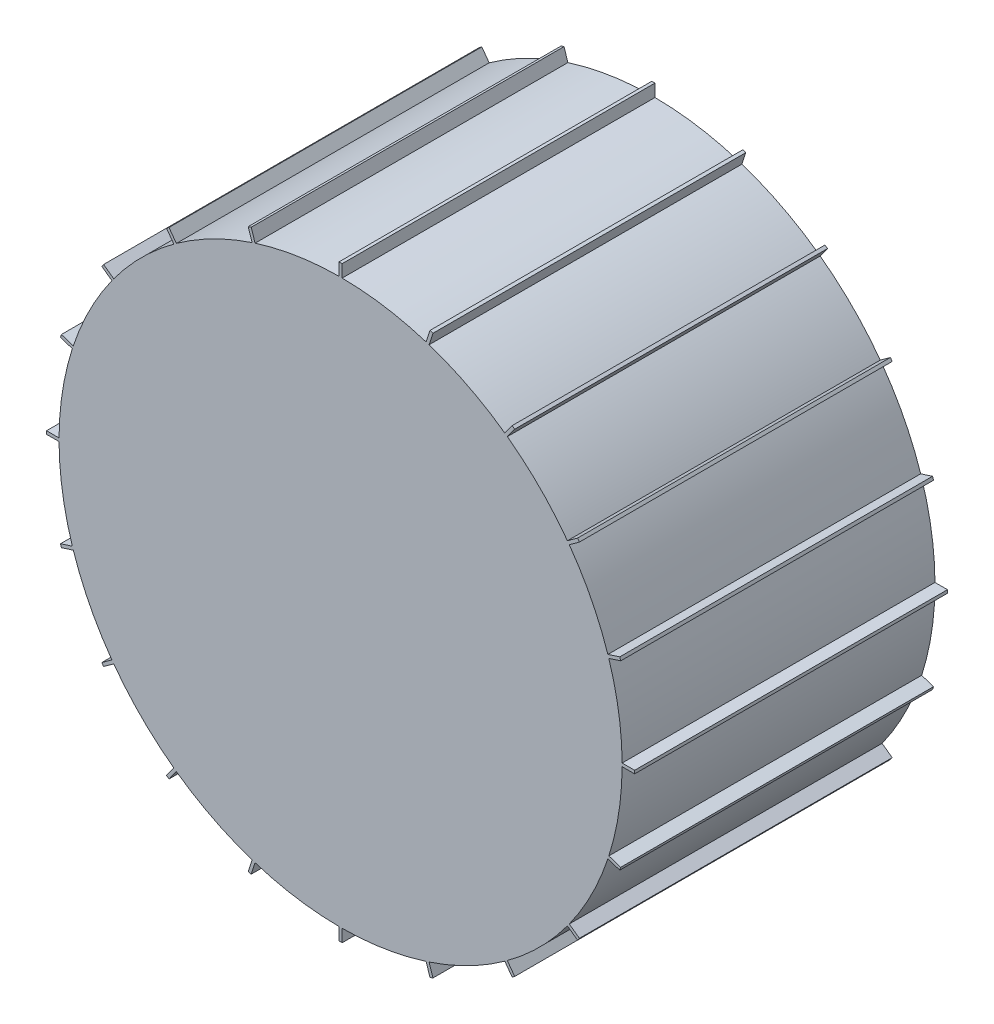
SolidWorks part; units mm, degrees
ref_plane "Front Plane" through (0, 0, 0) normal (0, 0, 1) x (1, 0, 0)
ref_plane "Top Plane" through (0, 0, 0) normal (0, 1, 0) x (1, 0, 0)
ref_plane "Right Plane" through (0, 0, 0) normal (1, 0, 0) x (0, 0, -1)
sketch "Sketch1" plane through (0, 0, 0) normal (0, 0, 1) x (1, 0, 0)
  circle A0 centre (0, 0) radius 450
  dimension "D1" = 900
extrude "Wheel Base" add sketch "Sketch1" along normal blind 500
ref_axis "Axis1" through (0, 0, 500) along (0, 0, -1)
sketch "Sketch3" plane through (0, 0, 0) normal (0, 1, 0) x (1, 0, 0)
  line L0 (0, 0) -> (0, -500) construction
  line L2 (2.5, -500) -> (-2.5, -500)
  line L3 (2.5, -500) -> (2.5, 0)
  line L4 (2.5, 0) -> (-2.5, 0)
  line L5 (-2.5, -500) -> (-2.5, 0)
  line L6 (2.5, -500) -> (-2.5, 0) construction
  line L7 (2.5, 0) -> (-2.5, -500) construction
  point P3 (0, -250)
  dimension "D1" = 500
  dimension "D2" = 500
  dimension "D3" = 5
extrude "Grouser" add sketch "Sketch3" along normal blind 470
pattern_circular "Grousers" count 20 over 360 about axis through (0, 0, 500) along (0, 0, -1) of "Grouser"
equation "\"Wheel_Diameter\"= 90cm"
equation "\"D1@Sketch1\"=\"Wheel_Diameter\""
equation "\"Wheel_Width\" = 50cm"
equation "\"D1@Wheel Base\"=\"Wheel_Width\""
equation "\"D1@Sketch3\"=\"Wheel_Width\""
equation "\"D2@Sketch3\"=\"Wheel_Width\""
equation "\"Grouser_width\" = 5mm"
equation "\"D3@Sketch3\"=\"Grouser_width\""
equation "\"Grouser_height\"= 20mm"
equation "\"D1@Grouser\" = \"Wheel_Diameter\" / 2 + \"Grouser_height\""
equation "\"Number_of_Grousers\" = 20"
equation "\"D1@Grousers\" = \"Number_of_Grousers\""
